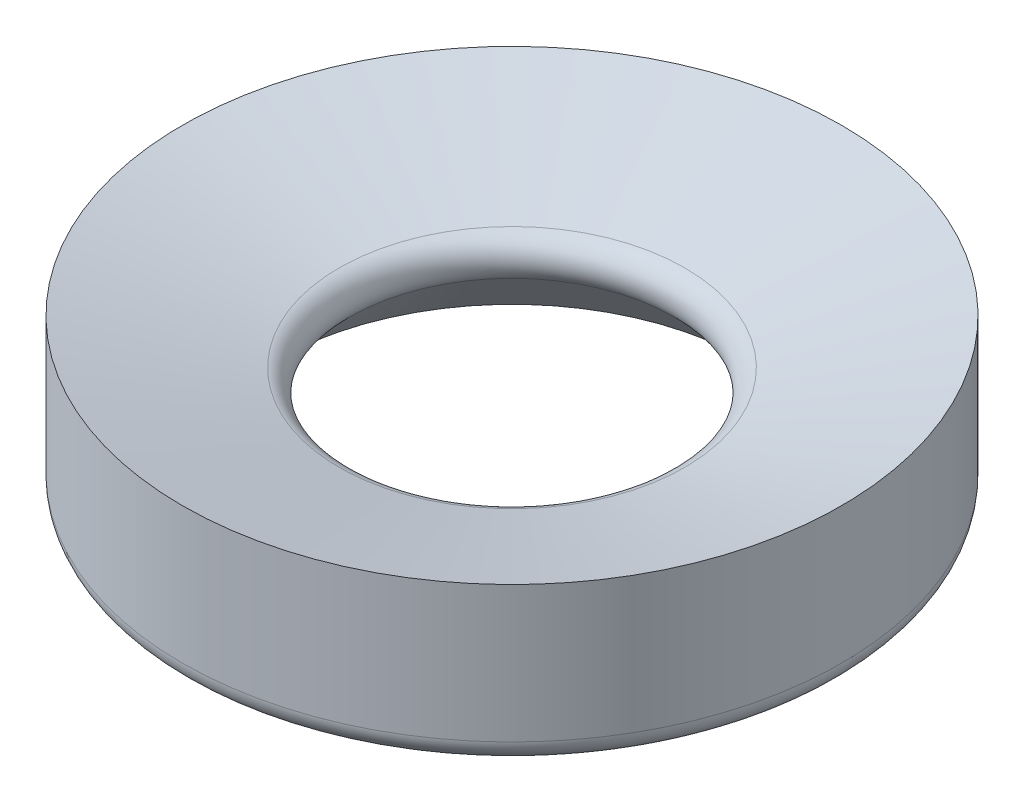
SolidWorks part; units mm, degrees
material "Nylon 101"
ref_plane "Front Plane" through (0, 0, 0) normal (0, 0, 1) x (1, 0, 0)
ref_plane "Top Plane" through (0, 0, 0) normal (0, 1, 0) x (1, 0, 0)
ref_plane "Right Plane" through (0, 0, 0) normal (1, 0, 0) x (0, 0, -1)
sketch "Sketch1" plane through (0, 0, 0) normal (0, 1, 0) x (1, 0, 0)
  circle A0 centre (0, 0) radius 36.83
extrude "Boss-Extrude1" add sketch "Sketch1" along normal blind 17.78
fillet "Fillet1" radius 2.54 1 edges at (0, 0, 36.83)
sketch "Sketch2" plane through (0, 0, 0) normal (0, 1, 0) x (1, 0, 0)
  circle A0 centre (0, 0) radius 26.67
  dimension "D1" = 53.34
ref_plane "Plane1" through (0, 11.938, 0) normal (0, 1, 0) x (1, 0, 0)
sketch "Sketch3" plane through (0, 11.938, 0) normal (0, 1, 0) x (1, 0, 0)
  circle A0 centre (0, 0) radius 14.7955
  dimension "D1" = 29.591
loft "Cut-Loft1" cut profiles "Sketch2", "Sketch3" connector at (-21.548, 0, -15.7154) connector at (-12.1049, 11.938, -8.5075)
sketch "Sketch4" plane through (0, 11.938, 0) normal (0, -1, 0) x (1, 0, 0)
  circle A0 centre (0, 0) radius 14.7955 construction
  circle A1 centre (0, 0) radius 14.7955
extrude "Cut-Extrude1" cut sketch "Sketch4" against normal blind 76.2
sketch "Sketch6" plane through (0, 17.78, 0) normal (0, 1, 0) x (1, 0, 0)
  circle A0 centre (0, 0) radius 36.83 construction
  circle A1 centre (0, 0) radius 36.83
ref_plane "Plane2" through (0, 11.43, 0) normal (0, 1, 0) x (1, 0, 0)
sketch "Sketch7" plane through (0, 11.43, 0) normal (0, 1, 0) x (1, 0, 0)
  circle A0 centre (0, 0) radius 14.7955 construction
  circle A1 centre (0, 0) radius 14.7955
loft "Cut-Loft2" cut profiles "Sketch7", "Sketch6" connector at (0.0583, 11.43, 14.7954) connector at (0, 17.78, 36.83)
sketch "Sketch8" plane through (0, 0, 0) normal (0, -1, 0) x (1, 0, 0)
  circle A0 centre (0, 0) radius 34.29 construction
  circle A1 centre (0, 0) radius 31.75
  circle A2 centre (0, 0) radius 26.67 construction
  circle A3 centre (0, 0) radius 29.21
  dimension "D1" = 2.54
  dimension "D2" = 2.54
extrude "Cut-Extrude2" cut sketch "Sketch8" against normal blind 2.54
fillet "Fillet3" radius 2.54 1 edges at (0, 0, -31.75)
fillet "Fillet4" radius 2.54 1 edges at (0, 0, -29.21)
fillet "Fillet5" radius 2.54 1 edges at (0, 11.5432, 15.1882)
